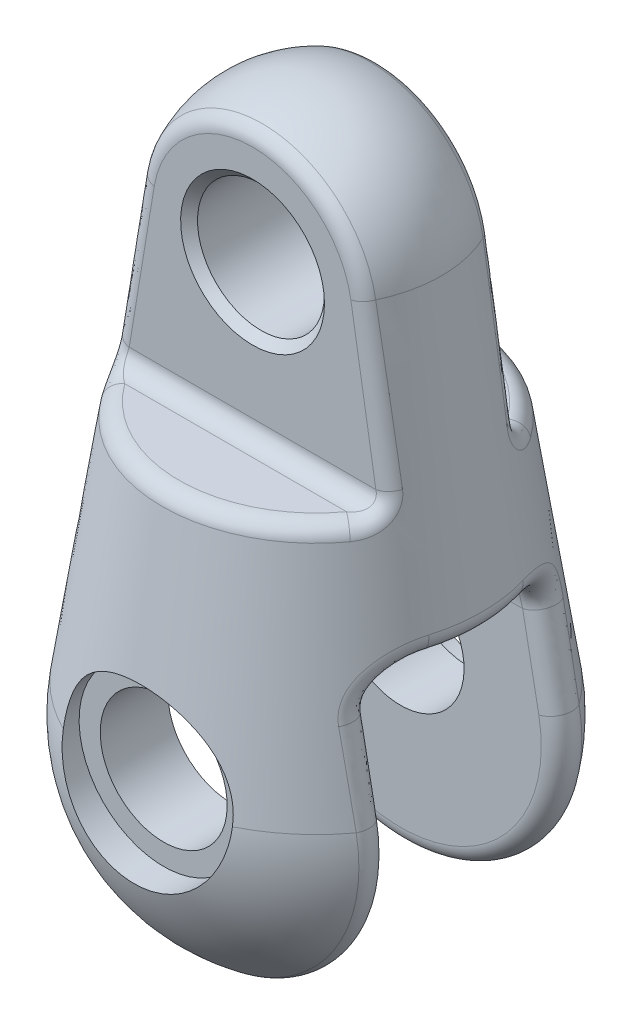
SolidWorks part; units mm, degrees
ref_plane "Plano frontal" through (0, 0, 0) normal (0, 0, 1) x (1, 0, 0)
ref_plane "Plano superior" through (0, 0, 0) normal (0, 1, 0) x (1, 0, 0)
ref_plane "Plano direito" through (0, 0, 0) normal (1, 0, 0) x (0, 0, -1)
sketch "Esboço1" plane through (0, 0, 0) normal (0, 0, 1) x (1, 0, 0)
  line L0 (0, 0) -> (0, 87.5)
  line L1 (-14.8303, 74.75) -> (-22.2454, 25.875)
  arc A1 (-22.2454, 25.875) -> (0, 0) centre (0, 22.5) ccw
  arc A2 (0, 87.5) -> (-14.8303, 74.75) centre (0, 72.5) ccw
  dimension "D2" = 30
  dimension "D3" = 45
  dimension "D1" = 87.5
revolve "Revolução1" add sketch "Esboço1" angle 360 about L0
sketch "Esboço2" plane through (0, 0, 0) normal (1, 0, 0) x (0, 0, -1)
  line L1 (27.5, 94.5) -> (7.5, 94.5)
  line L2 (27.5, 94.5) -> (27.5, 54.5)
  line L3 (27.5, 54.5) -> (7.5, 54.5)
  line L4 (7.5, 94.5) -> (7.5, 54.5)
  arc A0 (14.8303, 74.75) -> (-14.8303, 74.75) centre (0, 72.5) ccw construction
  dimension "D3" = 18
  dimension "D1" = 7.5
  dimension "D2" = 20
  dimension "D4" = 40
extrude "Corte-extrusão1" cut sketch "Esboço2" against normal mid plane 94 contours L1 L4 L3 L2
mirror "Espelhar1" about plane through (0, 0, 0) normal (0, 0, 1) of "Corte-extrusão1"
sketch "Esboço3" plane through (0, 0, 7.5) normal (0, 0, 1) x (1, 0, 0)
  circle A0 centre (0, 72.5) radius 7.5
  dimension "D1" = 15
extrude "Corte-extrusão2" cut sketch "Esboço3" against normal mid plane 94
chamfer "Chanfro1" distance 1 angle 45 2 edges at (0, 65, -7.5) (0, 65, 7.5)
fillet "Filete1" radius 2 10 edges at (0, 54.5, 17.9025) (0, 54.5, -17.9025) (0, 85.4904, 7.5) (0, 85.4904, -7.5) (0, 54.5, -7.5) (0, 54.5, 7.5)
sketch "Esboço4" plane through (0, 0, 0) normal (1, 0, 0) x (0, 0, -1)
  line L1 (-10, 40.5) -> (10, 40.5)
  line L2 (-10, 40.5) -> (-10, -9.5)
  line L3 (-10, -9.5) -> (10, -9.5)
  line L4 (10, 40.5) -> (10, -9.5)
  arc A0 (-22.2454, 25.875) -> (22.2454, 25.875) centre (0, 22.5) ccw construction
  dimension "D3" = 18
  dimension "D1" = 10
  dimension "D2" = 20
  dimension "D4" = 50
extrude "Corte-extrusão3" cut sketch "Esboço4" against normal mid plane 77
sketch "Esboço5" plane through (0, 0, 0) normal (1, 0, 0) x (0, 0, -1)
  line L0 (10, 25.875) -> (0, 25.875)
  line L1 (0, 25.875) -> (-30, 25.875)
  line L2 (-30, 25.875) -> (-30, 35.875)
  line L3 (-30, 35.875) -> (-18, 35.875)
  line L4 (-18, 35.875) -> (-18, 33.375)
  line L5 (-18, 33.375) -> (0, 33.375)
  line L6 (0, 33.375) -> (0, 25.875)
  line L7 (10, 40.5) -> (10, 25.875) construction
  point P3 (0, 0)
  point P9 (0, 0)
  point P11 (-0.0266, 21.4826)
  dimension "D1" = 10
  dimension "D2" = 7.5
  dimension "D3" = 18
  dimension "D4" = 30
  dimension "D5" = 40
revolve "Corte-Revolução1" cut sketch "Esboço5" angle 360 about L1 region at (0, 30.2132, 16.0588)
mirror "Espelhar2" about plane through (0, 0, 0) normal (0, 0, 1) of "Corte-Revolução1"
fillet "Filete2" radius 5 2 edges at (0, 40.5, 10) (0, 40.5, -10)
fillet "Filete3" radius 2 12 edges at (-18.458, 39.3275, 8.2172) (-20.0266, 40.5, 0) (-18.1936, 38.3074, -9.1374) (0, 2.3444, -10) (18.458, 39.3275, -8.2172) (20.0266, 40.5, 0) (18.1936, 38.3074, 9.1374) (0, 2.3444, 10)
